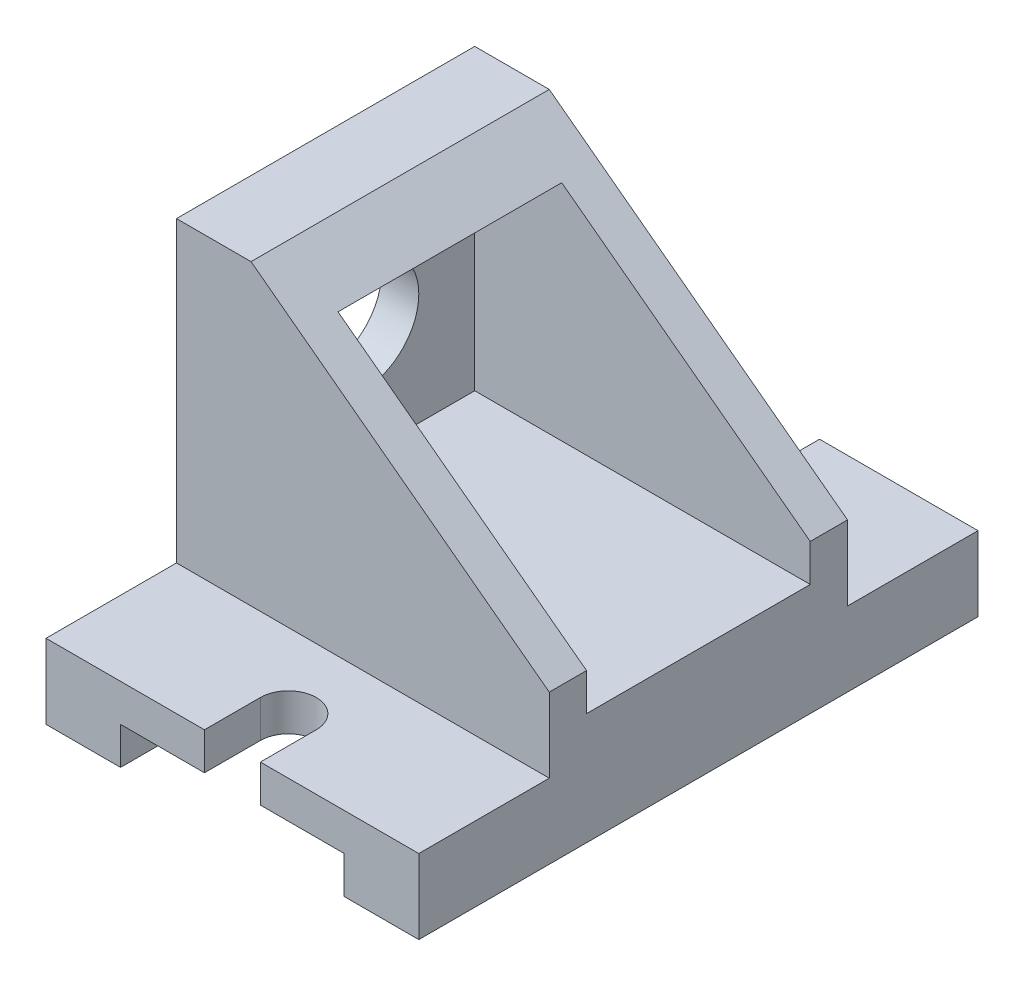
SolidWorks part; units mm, degrees
ref_plane "Front Plane" through (0, 0, 0) normal (0, 0, 1) x (1, 0, 0)
ref_plane "Top Plane" through (0, 0, 0) normal (0, 1, 0) x (1, 0, 0)
ref_plane "Right Plane" through (0, 0, 0) normal (1, 0, 0) x (0, 0, -1)
sketch "Sketch1" plane through (0, 0, 0) normal (0, 0, 1) x (1, 0, 0)
  line L1 (0, 0) -> (100, 0)
  line L2 (0, 0) -> (0, 100)
  line L3 (0, 100) -> (100, 100)
  line L4 (100, 0) -> (100, 100)
  dimension "D1" = 100
  dimension "D2" = 100
extrude "Boss-Extrude2" add sketch "Sketch1" against normal blind 150
sketch "Sketch2" plane through (0, 100, 0) normal (0, 1, 0) x (1, 0, 0)
  line L0 (100, 75) -> (0, 75) construction
  line L3 (42.5, 135) -> (42.5, 150)
  line L4 (100, 150) -> (0, 150) construction
  line L5 (57.5, 135) -> (57.5, 150)
  line L6 (100, 150) -> (100, 0) construction
  line L7 (0, 150) -> (100, 150)
  line L8 (0, 150) -> (0, 115)
  line L9 (0, 115) -> (100, 115)
  line L10 (100, 150) -> (100, 115)
  line L11 (57.5, 15) -> (57.5, 0)
  line L12 (42.5, 15) -> (42.5, 0)
  line L13 (0, 35) -> (100, 35)
  line L14 (100, 0) -> (100, 35)
  line L15 (0, 0) -> (100, 0)
  line L16 (0, 0) -> (0, 35)
  arc A0 (42.5, 135) -> (57.5, 135) centre (50, 135) ccw
  arc A1 (42.5, 15) -> (57.5, 15) centre (50, 15) cw
  line M12 (0, 0) -> (100, 0)
  line M13 (100, 0) -> (100, 150)
  line M14 (100, 150) -> (0, 150)
  line M15 (0, 150) -> (0, 0)
  dimension "D3" = 15
  dimension "D1" = 50
  dimension "D2" = 15
  dimension "D4" = 35
  dimension "D5" = 75
extrude "Cut-Extrude1" cut sketch "Sketch2" against normal blind 80 contours L12 A1 L11 L13 M12 M13 M15 | A0 L3 L9 L5 M14 M15 M13 region at (50, 100, -126.4405) region at (50, 100, -33.9405)
extrude "Cut-Extrude2" cut sketch "Sketch2<3>" against normal blind 103 contours A1 L12 L11 M12 | L3 A0 L5 M14 region at (50, 100, -139.4877) region at (50, 100, -10.5123)
sketch "Sketch2<3>" plane through (0, 100, 0) normal (0, 1, 0) x (1, 0, 0) same geometry as "Sketch2"
sketch "Sketch3" plane through (0, 0, 0) normal (0, 0, 1) x (1, 0, 0)
  line L0 (0, 0) -> (42.5, 0) construction
  line L1 (80, 10) -> (20, 10)
  line L2 (80, 10) -> (80, 0)
  line L3 (80, 0) -> (20, 0)
  line L4 (20, 10) -> (20, 0)
  dimension "D1" = 60
  dimension "D2" = 10
  dimension "D3" = 20
extrude "Cut-Extrude3" cut sketch "Sketch3" against normal blind 178
sketch "Sketch4" plane through (0, 0, -35) normal (0, 0, 1) x (1, 0, 0)
  line L0 (0, 0) -> (0, 100)
  line L1 (0, 100) -> (20, 100)
  line L2 (0, 100) -> (100, 100) construction
  line L3 (20, 100) -> (100, 40)
  line L4 (100, 20) -> (100, 100) construction
  line L5 (100, 40) -> (100, 0)
  line L6 (20, 100) -> (100, 100)
  line L7 (100, 100) -> (100, 40)
  line M4 (100, 100) -> (0, 100)
  line M7 (100, 20) -> (100, 100)
  dimension "D1" = 20
  dimension "D2" = 40
extrude "Cut-Extrude4" cut sketch "Sketch4" against normal blind 81 contours L3 M4 M7 region at (73.3333, 80, -35)
sketch "Sketch5" plane through (100, 0, 0) normal (1, 0, 0) x (0, 0, -1)
  line L0 (150, 0) -> (0, 0) construction
  line L1 (45, 90) -> (105, 90)
  line L2 (45, 90) -> (45, 30)
  line L3 (45, 30) -> (105, 30)
  line L4 (105, 90) -> (105, 30)
  line L5 (115, 100) -> (115, 40) construction
  circle A0 centre (75, 60) radius 15
  point P10 (0, 0)
  dimension "D6" = 30
  dimension "D1" = 30
  dimension "D2" = 60
  dimension "D3" = 10
  dimension "D4" = 60
  dimension "D5" = 40
extrude "Cut-Extrude5" cut sketch "Sketch5" against normal blind 90
sketch "Sketch6" plane through (100, 0, 0) normal (1, 0, 0) x (0, 0, -1)
  circle A0 centre (75, 60) radius 15
  dimension "D1" = 30
extrude "Cut-Extrude6" cut sketch "Sketch6" against normal blind 128
